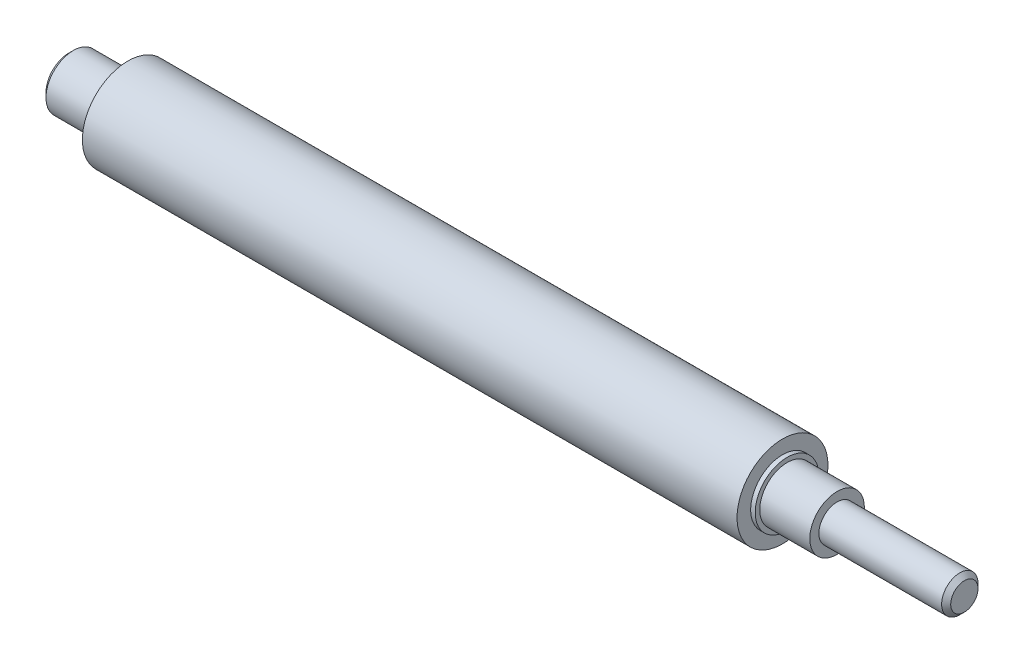
SolidWorks part; units mm, degrees
material "Brass"
ref_plane "Front Plane" through (0, 0, 0) normal (0, 0, 1) x (1, 0, 0)
ref_plane "Top Plane" through (0, 0, 0) normal (0, 1, 0) x (1, 0, 0)
ref_plane "Right Plane" through (0, 0, 0) normal (1, 0, 0) x (0, 0, -1)
sketch "Sketch1" plane through (0, 0, 0) normal (0, 0, 1) x (1, 0, 0)
  line L0 (0, 0) -> (0, 3)
  line L1 (0, 3) -> (6, 3)
  line L2 (6.5, 3.5) -> (6.5, 5)
  line L3 (6.5, 5) -> (78.5, 5)
  line L4 (78.5, 5) -> (78.5, 3.5)
  line L5 (79, 3) -> (84.5, 3)
  line L6 (84.5, 3) -> (84.5, 2)
  line L7 (84.5, 2) -> (98.5, 2)
  line L8 (98.5, 2) -> (98.5, 0)
  line L9 (98.5, 0) -> (0, 0)
  line L10 (78.5, 3.5) -> (79, 3.5)
  line L11 (79, 3.5) -> (79, 3)
  line L12 (6, 3) -> (6, 3.5)
  line L13 (6, 3.5) -> (6.5, 3.5)
  dimension "D1" = 3
  dimension "D2" = 5
  dimension "D3" = 73
  dimension "D4" = 0.5
  dimension "D5" = 20
  dimension "D6" = 6
  dimension "D7" = 2
  dimension "D8" = 6
revolve "Revolve1" add sketch "Sketch1" angle 360 about L9
chamfer "Chamfer1" distance 0.5 angle 45 2 edges at (0, 0, -3) (98.5, 0, -2)
